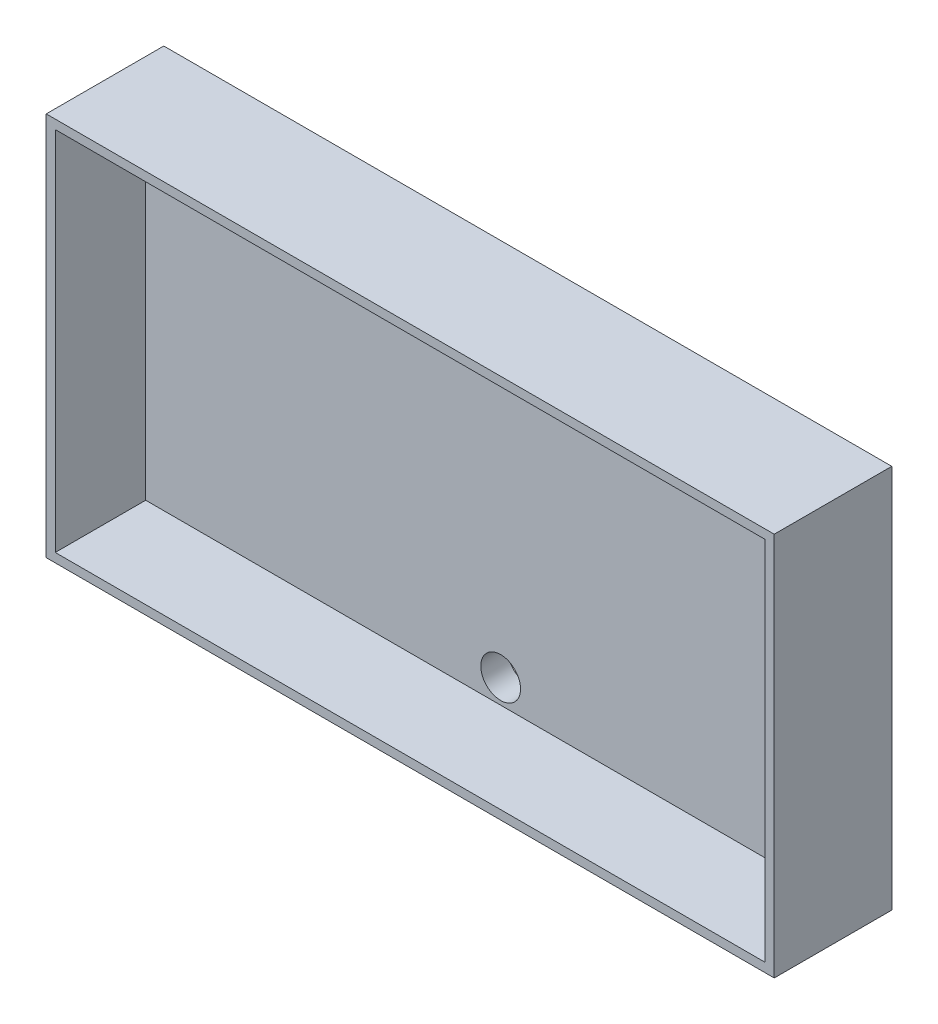
SolidWorks part; units mm, degrees
ref_plane "Front Plane" through (0, 0, 0) normal (0, 0, 1) x (1, 0, 0)
ref_plane "Top Plane" through (0, 0, 0) normal (0, 1, 0) x (1, 0, 0)
ref_plane "Right Plane" through (0, 0, 0) normal (1, 0, 0) x (0, 0, -1)
sketch "Sketch1" plane through (0, 0, 0) normal (0, 0, 1) x (1, 0, 0)
  line L0 (-1000, 0) -> (49000, 0) construction
  line L1 (-39.25, 20.25) -> (39.25, 20.25)
  line L2 (-39.25, 20.25) -> (-39.25, -20.25)
  line L3 (-39.25, -20.25) -> (39.25, -20.25)
  line L4 (39.25, 20.25) -> (39.25, -20.25)
  line L5 (0, -1000) -> (0, 49000) construction
  dimension "D1" = 78.5
  dimension "D2" = 40.5
extrude "Vysunout tenkostěnný1" add sketch "Sketch1" along normal blind 10 thin thin type one direction wall 1
sketch "Skica1" plane through (0, 0, 0) normal (0, 0, 1) x (1, 0, 0)
  line L0 (-40.25, -21.25) -> (40.25, -21.25) construction
  line L1 (-40.25, 21.25) -> (-40.25, -21.25) construction
  line L2 (40.25, -21.25) -> (40.25, 21.25) construction
  line L3 (40.25, 21.25) -> (-40.25, 21.25) construction
  line L4 (-40.25, -21.25) -> (40.25, -21.25)
  line L5 (-40.25, 21.25) -> (-40.25, -21.25)
  line L6 (40.25, -21.25) -> (40.25, 21.25)
  line L7 (40.25, 21.25) -> (-40.25, 21.25)
extrude "Přidat vysunutím1" add sketch "Skica1" against normal blind 3
sketch "Sketch3" plane through (0, 0, 0) normal (0, 0, 1) x (1, 0, 0)
  line L0 (-1000, 0) -> (49000, 0) construction
  circle A0 centre (0, -17.6) radius 2.2
  circle A1 centre (0, 17.6) radius 2.2
  point P4 (0, 0)
  dimension "D1" = 4.4
  dimension "D2" = 4.4
  dimension "D3" = 35.2
extrude "Cut-Extrude2" cut sketch "Sketch3" against normal through all both and the other way through all
